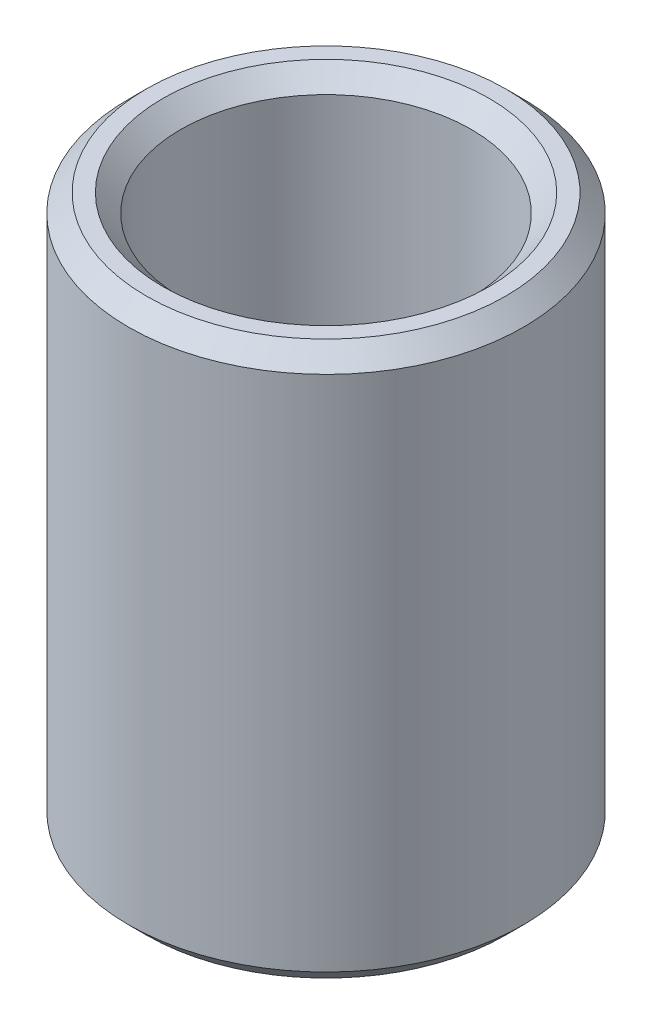
SolidWorks part; units mm, degrees
ref_plane "Front Plane" through (0, 0, 0) normal (0, 0, 1) x (1, 0, 0)
ref_plane "Top Plane" through (0, 0, 0) normal (0, 1, 0) x (1, 0, 0)
ref_plane "Right Plane" through (0, 0, 0) normal (1, 0, 0) x (0, 0, -1)
sketch "Sketch1" plane through (0, 0, 0) normal (0, 1, 0) x (1, 0, 0)
  circle A0 centre (0, 0) radius 42.5
  dimension "SLEEVE_OD" = 85
extrude "Boss-Extrude1" add sketch "Sketch1" along normal blind 119.096
sketch "Sketch2" plane through (0, 0, 0) normal (0, 1, 0) x (1, 0, 0)
  circle A0 centre (0, 0) radius 31.2515
  dimension "BORE_D" = 62.5029
extrude "Cut-Extrude1" cut sketch "Sketch2" along normal through all
chamfer "Chamfer1" distance 3.8533 angle 45 4 edges at (0, 119.096, 31.2515) (0, 0, 31.2515) (0, 0, 42.5) (0, 119.096, 42.5)
